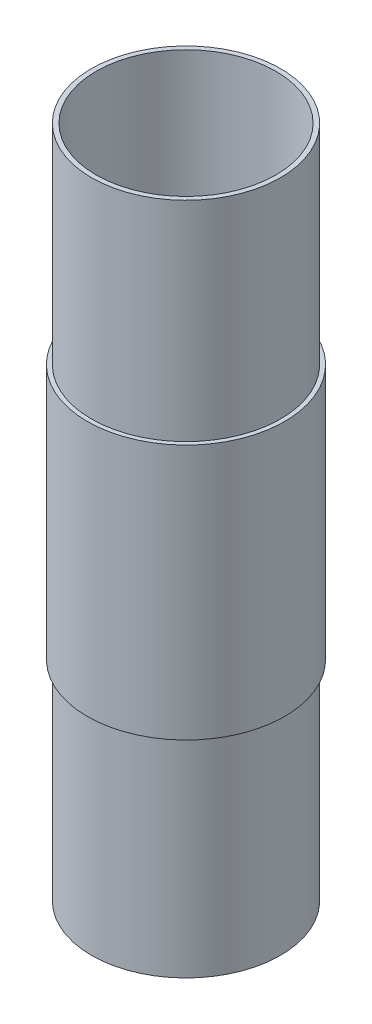
SolidWorks part; units mm, degrees
ref_plane "Front Plane" through (0, 0, 0) normal (0, 0, 1) x (1, 0, 0)
ref_plane "Top Plane" through (0, 0, 0) normal (0, 1, 0) x (1, 0, 0)
ref_plane "Right Plane" through (0, 0, 0) normal (1, 0, 0) x (0, 0, -1)
sketch "Sketch1" plane through (0, 0, 0) normal (0, 1, 0) x (1, 0, 0)
  circle A0 centre (0, 0) radius 42.5
  circle A1 centre (0, 0) radius 40.7
  circle A2 centre (0, 0) radius 38.7
  dimension "D1" = 85
  dimension "D2" = 81.4
  dimension "D3" = 2
extrude "Boss-Extrude1" add sketch "Sketch1" along normal mid plane 290 contours A1 A2 region at (-39.5488, 0, 0)
extrude "Boss-Extrude2" add sketch "Sketch1<3>" along normal mid plane 110 contours A0 A1 region at (-41.2979, 0, 0)
sketch "Sketch1<3>" plane through (0, 0, 0) normal (0, 1, 0) x (1, 0, 0) same geometry as "Sketch1"
